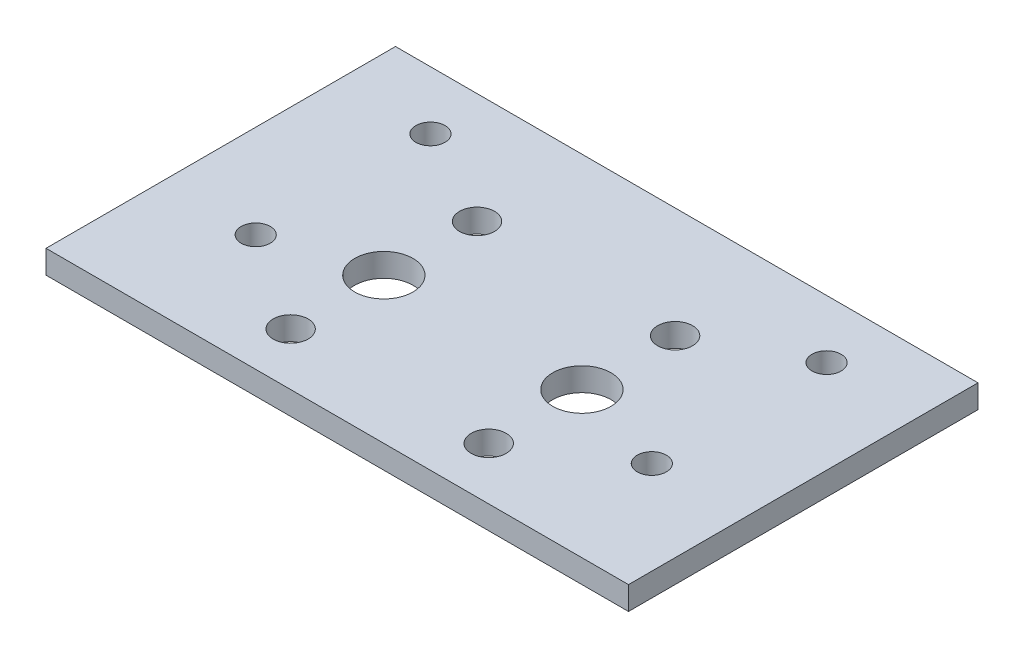
SolidWorks part; units mm, degrees
ref_plane "Спереди" through (0, 0, 0) normal (0, 0, 1) x (1, 0, 0)
ref_plane "Сверху" through (0, 0, 0) normal (0, 1, 0) x (1, 0, 0)
ref_plane "Справа" through (0, 0, 0) normal (1, 0, 0) x (0, 0, -1)
sketch "Эскиз1" plane through (0, 0, 0) normal (0, 1, 0) x (1, 0, 0)
  line L0 (16, 60) -> (16, 0) construction
  line L1 (0, 0) -> (100, 0)
  line L2 (0, 0) -> (0, 60)
  line L3 (0, 60) -> (100, 60)
  line L4 (100, 0) -> (100, 60)
  line L5 (84, 60) -> (84, 0) construction
  line L6 (33, 25) -> (67, 25) construction
  line L7 (50, 60) -> (50, 0) construction
  line L8 (33, 38.1007) -> (33, 6.4976) construction
  line L9 (67, 43.8556) -> (67, 6.4976) construction
  circle A0 centre (16, 50) radius 2.5
  circle A2 centre (16, 20) radius 2.5
  circle A3 centre (84, 50) radius 2.5
  circle A5 centre (84, 20) radius 2.5
  circle A6 centre (33, 25) radius 5
  circle A7 centre (67, 25) radius 5
  circle A8 centre (33, 41) radius 3
  circle A9 centre (33, 9) radius 3
  circle A10 centre (67, 41) radius 3
  circle A11 centre (67, 9) radius 3
  dimension "D5" = 5
  dimension "D7" = 5
  dimension "D12" = 10
  dimension "D13" = 10
  dimension "D17" = 6
  dimension "D18" = 6
  dimension "D19" = 6
  dimension "D20" = 6
  dimension "D1" = 100
  dimension "D2" = 60
  dimension "D3" = 16
  dimension "D4" = 16
  dimension "D8" = 10
  dimension "D14" = 17
  dimension "D15" = 17
  dimension "D16" = 35
  dimension "D21" = 16
  dimension "D22" = 16
  dimension "D23" = 16
  dimension "D24" = 16
  dimension "D11" = 2
extrude "Бобышка-Вытянуть1" add sketch "Эскиз1" along normal blind 4
